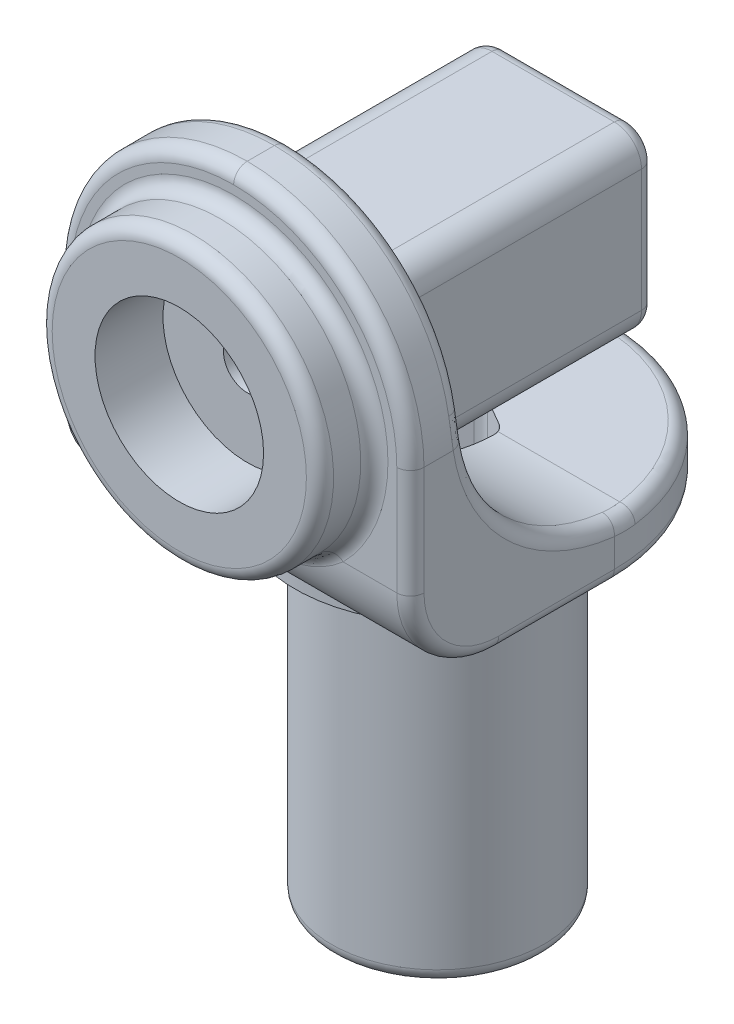
SolidWorks part; units mm, degrees
material "ABS"
ref_plane "정면" through (0, 0, 0) normal (0, 0, 1) x (1, 0, 0)
ref_plane "윗면" through (0, 0, 0) normal (0, 1, 0) x (1, 0, 0)
ref_plane "우측면" through (0, 0, 0) normal (1, 0, 0) x (0, 0, -1)
sketch "Sketch4" plane through (0, 0, 0) normal (1, 0, 0) x (0, 0, -1)
  line L0 (0, 0) -> (0, 576) construction
  line L1 (78, 521) -> (78, 271)
  line L2 (17.5, 576) -> (105, 576)
  line L4 (78, 521) -> (105, 521)
  line L5 (105, 576) -> (105, 521)
  line L6 (78, 271) -> (17.5, 271)
  line L7 (17.5, 271) -> (17.5, 576)
  dimension "D1" = 17.5
  dimension "D2" = 78
  dimension "D3" = 271
  dimension "D4" = 105
  dimension "D5" = 576
  dimension "D6" = 521
revolve "Revolve1" add sketch "Sketch4" angle 360 about L0
sketch "Sketch5" plane through (0, 0, 0) normal (-1, 0, 0) x (0, 0, 1)
  line L0 (105, 576) -> (-105, 576) construction
  line L9 (0, 0) -> (0, 681) construction
  line L10 (0, 681) -> (150, 681) construction
  line L11 (110, 701) -> (110, 811)
  line L12 (-130, 576) -> (-15, 576)
  line L13 (-130, 576) -> (-130, 536)
  line L14 (-130, 536) -> (85, 536)
  line L15 (150, 811) -> (150, 601)
  line L16 (110, 811) -> (150, 811)
  arc A2 (-15, 576) -> (110, 701) centre (-15, 701) ccw
  arc A3 (85, 536) -> (150, 601) centre (85, 601) ccw
  dimension "D1" = 40
  dimension "D2" = 40
  dimension "D7" = 125
  dimension "D8" = 65
  dimension "D3" = 130
  dimension "D4" = 130
  dimension "D5" = 681
  dimension "D6" = 150
extrude "Extrude1" add sketch "Sketch5" along normal mid plane 260
fillet "Fillet1" radius 130 2 edges at (130, 811, 130) (-130, 811, 130)
fillet "Fillet2" radius 130 2 edges at (130, 556, -130) (-130, 556, -130)
sketch "Sketch6" plane through (0, 0, 110) normal (0, 0, -1) x (-1, 0, 0)
  line L1 (-65, 616) -> (65, 616)
  line L2 (-65, 616) -> (-65, 746)
  line L3 (-65, 746) -> (65, 746)
  line L4 (65, 616) -> (65, 746)
  line L5 (-65, 616) -> (65, 746) construction
  line L6 (-65, 746) -> (65, 616) construction
  arc A0 (128.4523, 701) -> (0, 811) centre (0, 681) ccw construction
  point P0 (0, 681)
  dimension "D1" = 130
extrude "Extrude2" add sketch "Sketch6" along normal blind 205
fillet "Fillet3" radius 20 4 edges at (-65, 616, -9.1742) (65, 616, -9.1742) (65, 746, 7.5) (-65, 746, 7.5)
sketch "Sketch7" plane through (0, 0, 0) normal (1, 0, 0) x (0, 0, -1)
  line L0 (0, 681) -> (-150, 681) construction
  line L1 (-190, 784.5) -> (-110, 784.5)
  line L2 (-190, 784.5) -> (-190, 681)
  line L3 (-190, 681) -> (-110, 681)
  line L4 (-110, 784.5) -> (-110, 681)
  line L6 (-150, 811) -> (-150, 681) construction
  line L7 (-110, 701) -> (-110, 811) construction
  dimension "D1" = 103.5
  dimension "D2" = 40
revolve "Revolve2" add sketch "Sketch7" angle 360 about L3
sketch "Sketch8" plane through (0, 576, 0) normal (0, 1, 0) x (1, 0, 0)
  line L1 (0, 34.641) -> (-30, 17.3205)
  line L2 (-30, 17.3205) -> (-30, -17.3205)
  line L3 (-30, -17.3205) -> (0, -34.641)
  line L4 (0, -34.641) -> (30, -17.3205)
  line L5 (30, -17.3205) -> (30, 17.3205)
  line L6 (30, 17.3205) -> (0, 34.641)
  circle A0 centre (0, 0) radius 30 construction
  dimension "D1" = 60
extrude "Extrude3" cut sketch "Sketch8" against normal blind 205 and the other way up to surface other way up to face at (0, 616, -9.1742)
sketch "Sketch9" plane through (0, 0, 0) normal (1, 0, 0) x (0, 0, -1)
  line L0 (-140, 698.5) -> (95, 698.5)
  line L1 (-190, 681) -> (95, 681)
  line L2 (-190, 681) -> (-190, 743)
  line L3 (-190, 743) -> (-140, 743)
  line L4 (-140, 698.5) -> (-140, 743)
  line L5 (95, 698.5) -> (95, 681)
  line L6 (95, 726) -> (95, 636) construction
  dimension "D1" = 62
  dimension "D2" = 50
  dimension "D3" = 17.5
revolve "Cut-Revolve1" cut sketch "Sketch9" angle 360 about L1
sketch "Sketch10" plane through (0, 0, -95) normal (0, 0, -1) x (-1, 0, 0)
  line L1 (17.3205, 711) -> (-17.3205, 711)
  line L2 (-17.3205, 711) -> (-34.641, 681)
  line L3 (-34.641, 681) -> (-17.3205, 651)
  line L4 (-17.3205, 651) -> (17.3205, 651)
  line L5 (17.3205, 651) -> (34.641, 681)
  line L6 (34.641, 681) -> (17.3205, 711)
  circle A0 centre (0, 681) radius 30 construction
  dimension "D1" = 60
extrude "Extrude4" cut sketch "Sketch10" against normal blind 135
sketch "Sketch11" plane through (0, 371, 0) normal (0, 1, 0) x (1, 0, 0)
  line L0 (-30, -17.3205) -> (-30, 15) construction
  line L1 (-30, 0) -> (30, 0)
  line L2 (-30, 0) -> (-30, 150)
  line L3 (-30, 150) -> (30, 150)
  line L4 (30, 0) -> (30, 150)
  dimension "D1" = 150
extrude "Extrude5" cut sketch "Sketch11" along normal blind 50
fillet "Fillet4" radius 10 6 edges at (17.3205, 711, -27.5) (34.641, 681, -27.5) (17.3205, 651, -27.5) (-17.3205, 651, -27.5) (-34.641, 681, -27.5) (-17.3205, 711, -27.5)
fillet "Fillet5" radius 10 6 edges at (30, 475.6254, 17.3205) (30, 498.5, -17.3205) (0, 498.5, -34.641) (-30, 498.5, -17.3205) (-30, 475.6254, 17.3205) (0, 478.6398, 34.641)
fillet "Fillet6" radius 10 1 edges at (0, 271, -78)
fillet "Fillet7" radius 10 10 edges at (-59.1421, 740.1421, 110) (-65, 713.5, 110) (-65, 667.2461, 105.3564) (-58.4627, 621.2096, 81.221) (0, 616, 76.6515) (55.2089, 618.8018, 79.1725) (65, 667.2461, 105.3564) (65, 713.5, 110) (59.1421, 740.1421, 110) (0, 746, 110)
fillet "Fillet8" radius 10 8 edges at (-59.1421, 740.1421, -95) (-65, 681, -95) (-59.1421, 621.8579, -95) (0, 616, -95) (59.1421, 621.8579, -95) (65, 681, -95) (59.1421, 740.1421, -95) (0, 746, -95)
fillet "Fillet9" radius 10 10 edges at (-84.5577, 779.7421, 110) (-130, 610.8443, 71.585) (-86.4581, 576, -97.0824) (86.4581, 576, -97.0824) (130, 610.8443, 71.585) (84.5577, 779.7421, 110)
fillet "Fillet10" radius 10 10 edges at (130, 641, 150) (130, 555.0381, 130.9619) (130, 536, 42.5) (91.9239, 536, -91.9239) (-91.9239, 536, -91.9239) (-130, 536, 42.5) (-130, 555.0381, 130.9619) (-130, 641, 150) (-91.9239, 772.9239, 150) (91.9239, 772.9239, 150)
fillet "Fillet11" radius 10 1 edges at (103.5, 681, 190)
fillet "Fillet12" radius 10 2 edges at (-1.5363, 539.1498, 104.9888) (0, 536, -105)
fillet "Fillet13" radius 10 2 edges at (-4.7776, 577.6103, 145.6459) (0, 784.5, 150)
scale "Scale1" bodies to scale 110 scale about origin uniform scaling yes scale factor 0.1
equation "\"Mass\"= \"SW-질량\" / 1000"
